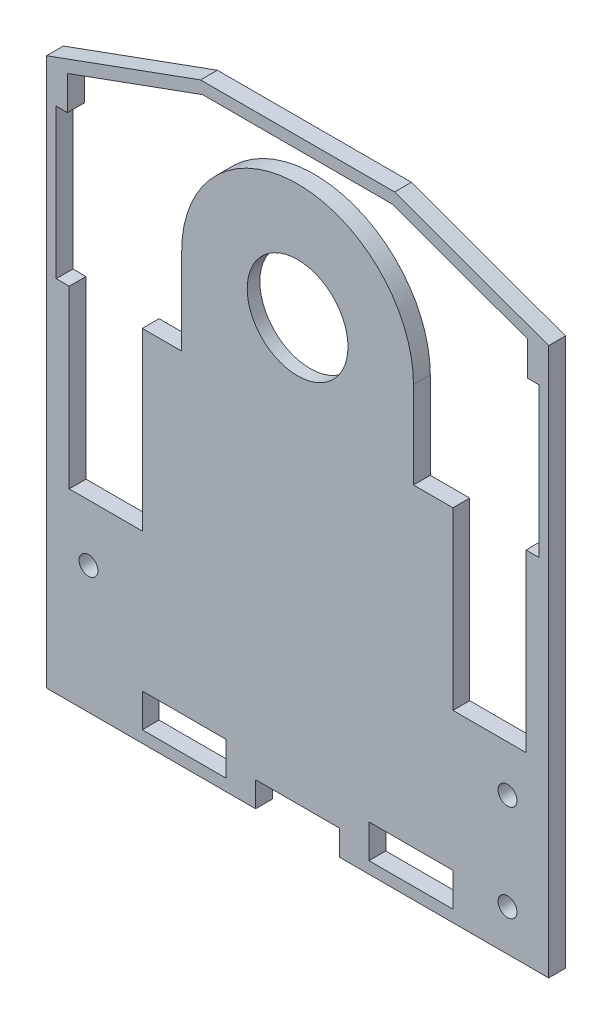
SolidWorks part; units mm, degrees
ref_plane "Front Plane" through (0, 0, 0) normal (0, 0, 1) x (1, 0, 0)
ref_plane "Top Plane" through (0, 0, 0) normal (0, 1, 0) x (1, 0, 0)
ref_plane "Right Plane" through (0, 0, 0) normal (1, 0, 0) x (0, 0, -1)
sketch "Sketch1" plane through (0, 0, -369.3563) normal (0, 0, 1) x (1, 0, 0)
  line L0 (14.5255, 48.5357) -> (32.8677, 41.8597)
  line L1 (32.8677, 41.8597) -> (32.8677, -23.3643)
  line L2 (32.8677, -23.3643) -> (-26.9323, -23.3643)
  line L3 (-26.9323, -23.3643) -> (-26.9323, 41.8597)
  line L4 (-26.9323, 41.8597) -> (-8.59, 48.5357)
  line L5 (-8.59, 48.5357) -> (14.5255, 48.5357)
  line L6 (-24.4323, 41.2798) -> (-8.3431, 47.1357)
  line L7 (-8.3431, 47.1357) -> (14.2786, 47.1357)
  line L8 (14.2786, 47.1357) -> (30.3677, 41.2798)
  line L9 (30.3677, 41.2798) -> (30.3677, 19.4357)
  line L15 (-24.4323, 19.4357) -> (-24.4323, 41.2798)
  line L17 (-10.8323, 19.4357) -> (-10.8323, 29.7857)
  line L19 (16.7677, 19.4357) -> (16.7677, 29.7857)
  line L20 (30.3677, 19.4357) -> (16.7677, 19.4357)
  line L21 (-10.8323, 19.4357) -> (-24.4323, 19.4357)
  line L22 (30.1677, 19.4357) -> (21.4677, 19.4357) construction
  line L23 (-15.5323, 19.4357) -> (-24.2323, 19.4357) construction
  line L24 (-15.5323, -1.4643) -> (-24.2323, -1.4643)
  line L25 (-24.2323, -1.4643) -> (-24.2323, 19.4357)
  line L26 (-24.2323, 19.4357) -> (-15.5323, 19.4357)
  line L27 (-15.5323, 19.4357) -> (-15.5323, -1.4643)
  line L28 (30.1677, -1.4643) -> (30.1677, 19.4357)
  line L29 (30.1677, 19.4357) -> (21.4677, 19.4357)
  line L30 (21.4677, 19.4357) -> (21.4677, -1.4643)
  line L31 (21.4677, -1.4643) -> (30.1677, -1.4643)
  line L32 (-15.5323, -21.9643) -> (-5.5323, -21.9643)
  line L33 (-5.5323, -21.9643) -> (-5.5323, -17.9643)
  line L34 (-5.5323, -21.9643) -> (-5.5323, 13.1357) construction
  line L35 (-5.5323, -17.9643) -> (-15.5323, -17.9643)
  line L36 (-15.5323, -21.9643) -> (-15.5323, -1.4643) construction
  line L37 (-15.5323, -17.9643) -> (-15.5323, -21.9643)
  line L38 (11.4677, -21.9643) -> (21.4677, -21.9643)
  line L39 (21.4677, -21.9643) -> (21.4677, -17.9643)
  line L40 (21.4677, -1.4643) -> (21.4677, -21.9643) construction
  line L41 (21.4677, -17.9643) -> (11.4677, -17.9643)
  line L42 (11.4677, 13.1357) -> (11.4677, -21.9643) construction
  line L43 (11.4677, -17.9643) -> (11.4677, -21.9643)
  arc A0 (-10.8323, 29.7857) -> (16.7677, 29.7857) centre (2.9677, 29.7857) cw
  circle A1 centre (2.9677, 29.7857) radius 6
  circle A2 centre (27.9677, -6.9643) radius 1.125
  circle A3 centre (-22.0323, -6.9643) radius 1.125
  circle A4 centre (27.9677, -18.4643) radius 1.125
  line M2 (-24.4323, 37.2357) -> (-24.4323, 41.2798)
  line M3 (-24.4323, 41.2798) -> (-8.3431, 47.1357)
  line M4 (-8.3431, 47.1357) -> (14.2786, 47.1357)
  line M5 (14.2786, 47.1357) -> (30.3677, 41.2798)
  line M6 (30.3677, 41.2798) -> (30.3677, 37.2357)
  line M10 (30.1677, 19.4357) -> (30.1677, -1.4643)
  line M11 (30.1677, -1.4643) -> (21.4677, -1.4643)
  line M12 (21.4677, -1.4643) -> (21.4677, -21.9643)
  line M13 (21.4677, -21.9643) -> (11.4677, -21.9643)
  line M14 (11.4677, -21.9643) -> (11.4677, 13.1357)
  arc M15 (11.4677, 13.1357) -> (12.5677, 16.7857) centre (17.3066, 13.3668) cw
  arc M16 (12.5677, 16.7857) -> (16.7677, 29.7857) centre (-5.4513, 29.7857) ccw
  arc M17 (16.7677, 29.7857) -> (-10.8323, 29.7857) centre (2.9677, 29.7857) ccw
  arc M18 (-10.8323, 29.7857) -> (-6.6323, 16.7857) centre (11.3868, 29.7857) ccw
  arc M19 (-6.6323, 16.7857) -> (-5.5323, 13.1357) centre (-11.3711, 13.3668) cw
  line M20 (-5.5323, 13.1357) -> (-5.5323, -21.9643)
  line M21 (-5.5323, -21.9643) -> (-15.5323, -21.9643)
  line M22 (-15.5323, -21.9643) -> (-15.5323, -1.4643)
  line M23 (-15.5323, -1.4643) -> (-24.2323, -1.4643)
  line M24 (-24.2323, -1.4643) -> (-24.2323, 19.4357)
  line M28 (-8.59, 48.5357) -> (-26.9323, 41.8597)
  line M29 (-26.9323, 41.8597) -> (-26.9323, -23.3643)
  line M30 (-26.9323, -23.3643) -> (-3.5323, -23.3643)
  line M31 (32.8677, -23.3643) -> (32.8677, 41.8597)
  line M32 (32.8677, 41.8597) -> (14.5255, 48.5357)
  line M33 (14.5255, 48.5357) -> (-8.59, 48.5357)
  line M63 (-25.7823, 37.2357) -> (-24.4323, 37.2357)
  line M64 (30.3677, 37.2357) -> (31.7177, 37.2357)
  line M65 (31.7177, 37.2357) -> (31.7177, 19.4357)
  line M66 (31.7177, 19.4357) -> (30.1677, 19.4357)
  line M67 (-24.2323, 19.4357) -> (-25.7823, 19.4357)
  line M68 (-25.7823, 19.4357) -> (-25.7823, 37.2357)
  dimension "D1" = 12
  dimension "D6" = 2.25
  dimension "D8" = 2.25
  dimension "D9" = 2.25
  dimension "D2" = 0
  dimension "D3" = 0
  dimension "D4" = 4
  dimension "D5" = 4
  dimension "D7" = 4.9
extrude "Boss-Extrude1" add sketch "Sketch1" along normal blind 2 contours M33 M28 M29 M30 M31 M32 M68 M63 M2 M3 M4 M5 M6 M64 M65 M66 M10 M11 M12 M13 M14 M15 M16 M17 M18 M19 M20 M21 M22 M23 M24 M67 | L21 L27 L17 M22 M21 M20 M19 M18 | L30 L20 L19 M16 M15 M14 M13 M12 | A1 | A3 | A3 | A4 | A2 region at (2.9173, 6.548, -369.3563) region at (-10.5913, 0.9312, -369.3563) region at (16.5268, 0.9312, -369.3563) region at (27.9677, -6.9643, -369.3563) region at (-22.0323, -6.9643, -369.3563) region at (27.9677, -18.4643, -369.3563)
sketch "Sketch2" plane through (0, 0, -369.3563) normal (0, 0, -1) x (-1, 0, 0)
  circle A0 centre (-2.9677, 29.7857) radius 12.875
  dimension "D1" = 25.75
extrude "Cut-Extrude1" cut sketch "Sketch2" against normal blind 0.5
sketch "Sketch3" plane through (0, 0, -367.3563) normal (0, 0, 1) x (1, 0, 0)
  circle A0 centre (27.9677, -6.9643) radius 1.125
  circle A1 centre (27.9677, -18.4643) radius 1.125
  circle A2 centre (-21.9323, -8.2143) radius 1.125
  dimension "D2" = 2.25
  dimension "D3" = 2.25
  dimension "D4" = 2.25
extrude "Cut-Extrude2" cut sketch "Sketch3" against normal through all
sketch "Sketch4" plane through (0, 0, -367.3563) normal (0, 0, 1) x (1, 0, 0)
  line L0 (-2.0323, -23.3643) -> (7.9677, -23.3643)
  line L1 (-26.9323, -23.3643) -> (32.8677, -23.3643) construction
  line L2 (7.9677, -23.3643) -> (7.9677, -20.3643)
  line L3 (7.9677, -20.3643) -> (-2.0323, -20.3643)
  line L4 (-2.0323, -20.3643) -> (-2.0323, -23.3643)
  point P0 (2.9677, -23.3643)
  point P5 (2.9677, -23.3643)
  dimension "D1" = 10
  dimension "D2" = 3
extrude "Cut-Extrude3" cut sketch "Sketch4" against normal through all
equation "\"M2_screw_head_hole\"= 4.5"
equation "\"D3@Sketch11\"=\"M2_screw_head_hole\""
equation "\"M2_screw_shaft_hole\"=2.25"
equation "\"D4@Sketch11\"=\"M2_screw_shaft_hole\""
equation "\"D1@Sketch11\"=\"M2_screw_head_hole\""
equation "\"D2@Sketch11\"=\"M2_screw_shaft_hole\""
equation "\"D1@Sketch9\"=\"M2_screw_head_hole\""
equation "\"D4@Sketch9\"=\"M2_screw_head_hole\""
equation "\"D2@Sketch9\"=\"M2_screw_head_hole\""
equation "\"D3@Sketch9\"=\"M2_screw_head_hole\""
equation "\"D32@Sketch6\"=\"M2_screw_shaft_hole\""
equation "\"D33@Sketch6\"=\"M2_screw_shaft_hole\""
equation "\"D34@Sketch6\"=\"M2_screw_shaft_hole\""
equation "\"D35@Sketch6\"=\"M2_screw_shaft_hole\""
equation "\"D14@Sketch2\"=\"M2_screw_shaft_hole\""
equation "\"D13@Sketch2\"=\"M2_screw_shaft_hole\""
equation "\"D13@Sketch3\"=\"M2_screw_shaft_hole\""
equation "\"D14@Sketch3\"=\"M2_screw_shaft_hole\""
equation "\"D14@Sketch4\"=\"M2_screw_shaft_hole\""
equation "\"D13@Sketch4\"=\"M2_screw_shaft_hole\""
equation "\"D6@Sketch1\"=\"M2_screw_shaft_hole\""
equation "\"D8@Sketch1\"=\"M2_screw_shaft_hole\""
equation "\"D9@Sketch1\"=\"M2_screw_shaft_hole\""
equation "\"D2@Sketch3\"=\"M2_screw_shaft_hole\""
equation "\"D3@Sketch3\"=\"M2_screw_shaft_hole\""
equation "\"D4@Sketch3\"=\"M2_screw_shaft_hole\""
